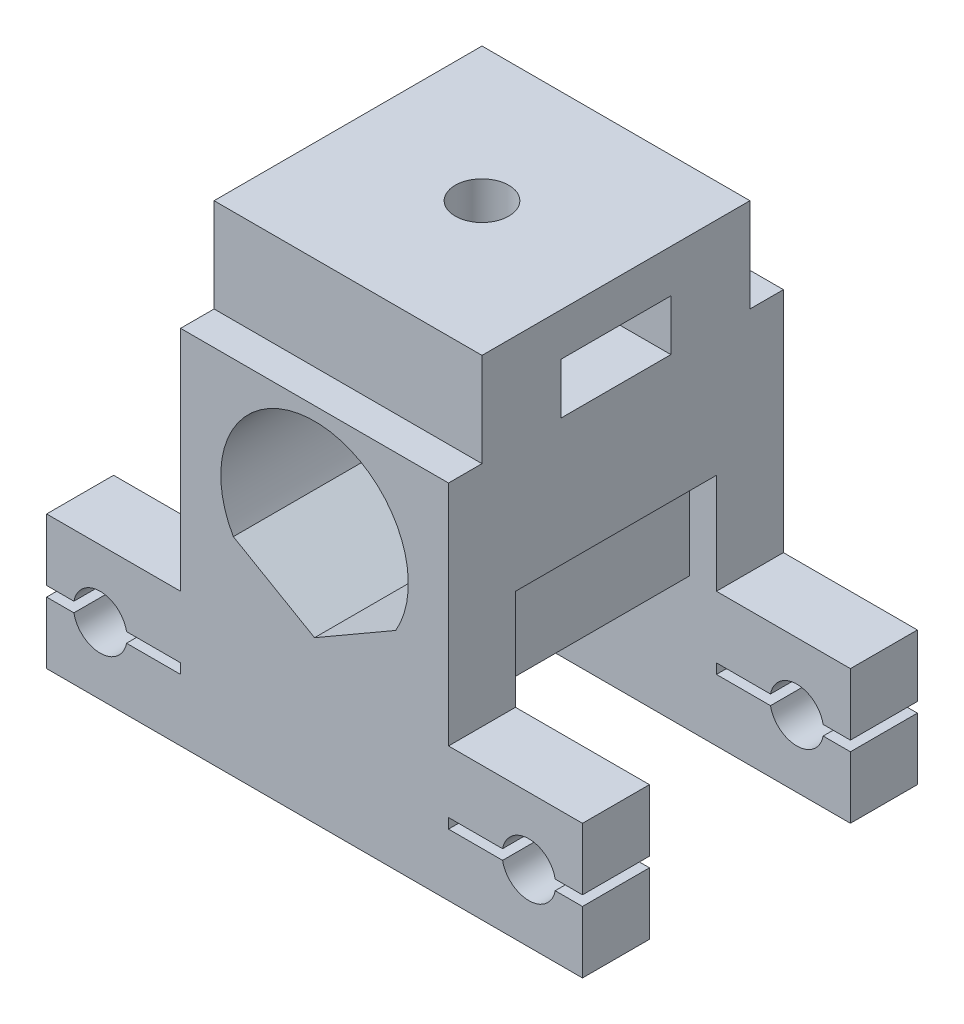
SolidWorks part; units mm, degrees
ref_plane "Front Plane" through (0, 0, 0) normal (0, 0, 1) x (1, 0, 0)
ref_plane "Top Plane" through (0, 0, 0) normal (0, 1, 0) x (1, 0, 0)
ref_plane "Right Plane" through (0, 0, 0) normal (1, 0, 0) x (0, 0, -1)
sketch "Sketch1" plane through (0, 0, 0) normal (0, 1, 0) x (1, 0, 0)
  line L1 (-10, -12.5) -> (10, -12.5)
  line L2 (-10, -12.5) -> (-10, 12.5)
  line L3 (-10, 12.5) -> (10, 12.5)
  line L4 (10, -12.5) -> (10, 12.5)
  line L5 (-10, -12.5) -> (10, 12.5) construction
  line L6 (-10, 12.5) -> (10, -12.5) construction
  point P0 (0, 0)
  dimension "D1" = 20
  dimension "D2" = 25
extrude "Boss-Extrude1" add sketch "Sketch1" along normal blind 17
sketch "Sketch2" plane through (0, 0, 12.5) normal (0, 0, 1) x (1, 0, 0)
  line L0 (0, 2) -> (-6.0622, 5.5)
  line L1 (-10, 0) -> (10, 0) construction
  line L2 (0, 2) -> (-6.4072, 2) construction
  line L3 (0, 17) -> (0, 16) construction
  line L4 (0, -55) -> (0, 55) construction
  line L5 (-10, 17) -> (10, 17) construction
  line L7 (0, 9) -> (0, 2) construction
  line L8 (0, 2) -> (6.0622, 5.5)
  arc A0 (6.0622, 5.5) -> (-6.0622, 5.5) centre (0, 9) ccw
  dimension "D1" = 2
  dimension "D2" = 3.5
  dimension "D3" = 30
extrude "Cut-Extrude1" cut sketch "Sketch2" against normal through all
ref_plane "Plane1" through (0, 0, 1.5) normal (0, 0, 1) x (1, 0, 0)
sketch "Sketch3" plane through (0, 0, 12.5) normal (0, 0, 1) x (1, 0, 0)
  line L0 (10, 0) -> (20, 0)
  line L1 (20, 0) -> (20, -10)
  line L2 (20, -10) -> (-20, -10)
  line L3 (-20, -10) -> (-20, 0)
  line L4 (-20, 0) -> (-10, 0)
  line L5 (-10, 0) -> (10, 0)
  dimension "D1" = 10
  dimension "D2" = 10
  dimension "D3" = 10
extrude "Boss-Extrude2" add sketch "Sketch3" against normal blind 5
mirror "Mirror1" about plane through (0, 0, 0) normal (0, 0, 1) of "Boss-Extrude2"
sketch "Sketch4" plane through (0, 0, 12.5) normal (0, 0, 1) x (1, 0, 0)
  line L0 (20, -10) -> (20, 0) construction
  line L1 (20, 0) -> (10, 0) construction
  line L2 (0, -13.75) -> (0, 13.75) construction
  circle A0 centre (16, -5) radius 2
  circle A1 centre (-16, -5) radius 2
  dimension "D1" = 4
  dimension "D2" = 4
  dimension "D3" = 5
extrude "Cut-Extrude2" cut sketch "Sketch4" against normal through all
sketch "Sketch6" plane through (0, 17, 0) normal (0, 1, 0) x (1, 0, 0)
  line L0 (10, -12.5) -> (10, 12.5) construction
  line L1 (-10, -10) -> (10, -10)
  line L2 (-10, -10) -> (-10, 10)
  line L3 (-10, 10) -> (10, 10)
  line L4 (10, -10) -> (10, 10)
  line L5 (-10, -10) -> (10, 10) construction
  line L6 (-10, 10) -> (10, -10) construction
  point P0 (0, 0)
  dimension "D1" = 20
extrude "Boss-Extrude3" add sketch "Sketch6" along normal blind 7 contours L2 L1 L4 L3
sketch "Sketch8" plane through (10, 0, 0) normal (1, 0, 0) x (0, 0, -1)
  line L0 (10, 17) -> (12.5, 17) construction
  line L5 (-4.1, 17) -> (4.1, 17)
  line L6 (-4.1, 17) -> (-4.1, 20.8)
  line L7 (-4.1, 20.8) -> (4.1, 20.8)
  line L8 (4.1, 17) -> (4.1, 20.8)
  line L9 (-4.1, 17) -> (4.1, 20.8) construction
  line L10 (-4.1, 20.8) -> (4.1, 17) construction
  line L11 (-10, 24) -> (-10, 17) construction
  point P0 (0, 18.9)
  dimension "D1" = 8.2
  dimension "D2" = 3.8
  dimension "D3" = 5.9
extrude "Cut-Extrude3" cut sketch "Sketch8" against normal through all
sketch "Sketch7" plane through (0, 24, 0) normal (0, 1, 0) x (1, 0, 0)
  circle A0 centre (0, 0) radius 2
extrude "Cut-Extrude4" cut sketch "Sketch7" against normal up to surface (8 mm away) up to face at (0, 10.75, 0)
sketch "Sketch9" plane through (10, 0, 0) normal (-1, 0, 0) x (0, 0, 1)
  line L0 (-12.5, 0) -> (-7.5, 0) construction
  line L1 (-7.5, 0) -> (7.5, 0)
  line L2 (-7.5, 0) -> (-7.5, 7.5)
  line L3 (-7.5, 7.5) -> (7.5, 7.5)
  line L4 (7.5, 0) -> (7.5, 7.5)
  dimension "D1" = 7.5
extrude "Cut-Extrude5" cut sketch "Sketch9" along normal blind 2
sketch "Sketch10" plane through (0, 0, 12.5) normal (0, 0, 1) x (1, 0, 0)
  line L0 (-20, 0) -> (-20, -10) construction
  line L1 (-20, -4.625) -> (-10, -4.625)
  line L2 (-20, -4.625) -> (-20, -5.375)
  line L3 (-20, -5.375) -> (-10, -5.375)
  line L4 (-10, -4.625) -> (-10, -5.375)
  line L5 (0, -0.8665) -> (0, -10) construction
  line L6 (-20, -10) -> (20, -10) construction
  line L7 (20, -4.625) -> (20, -5.375)
  line L8 (10, -4.625) -> (10, -5.375)
  line L9 (20, -5.375) -> (10, -5.375)
  line L10 (20, -4.625) -> (10, -4.625)
  circle A0 centre (-16, -5) radius 2 construction
  dimension "D1" = 0.75
  dimension "D2" = 0.375
  dimension "D3" = 10
extrude "Cut-Extrude6" cut sketch "Sketch10" against normal through all
extrude "Cut-Extrude7" cut sketch "Sketch9<2>" against normal offset from surface (2.5 mm away) 2.5 from surface up to face at (-10, 18.9, 0) starting at face at (-10, 18.9, 0)
sketch "Sketch9<2>" plane through (10, 0, 0) normal (-1, 0, 0) x (0, 0, 1) same geometry as "Sketch9"
